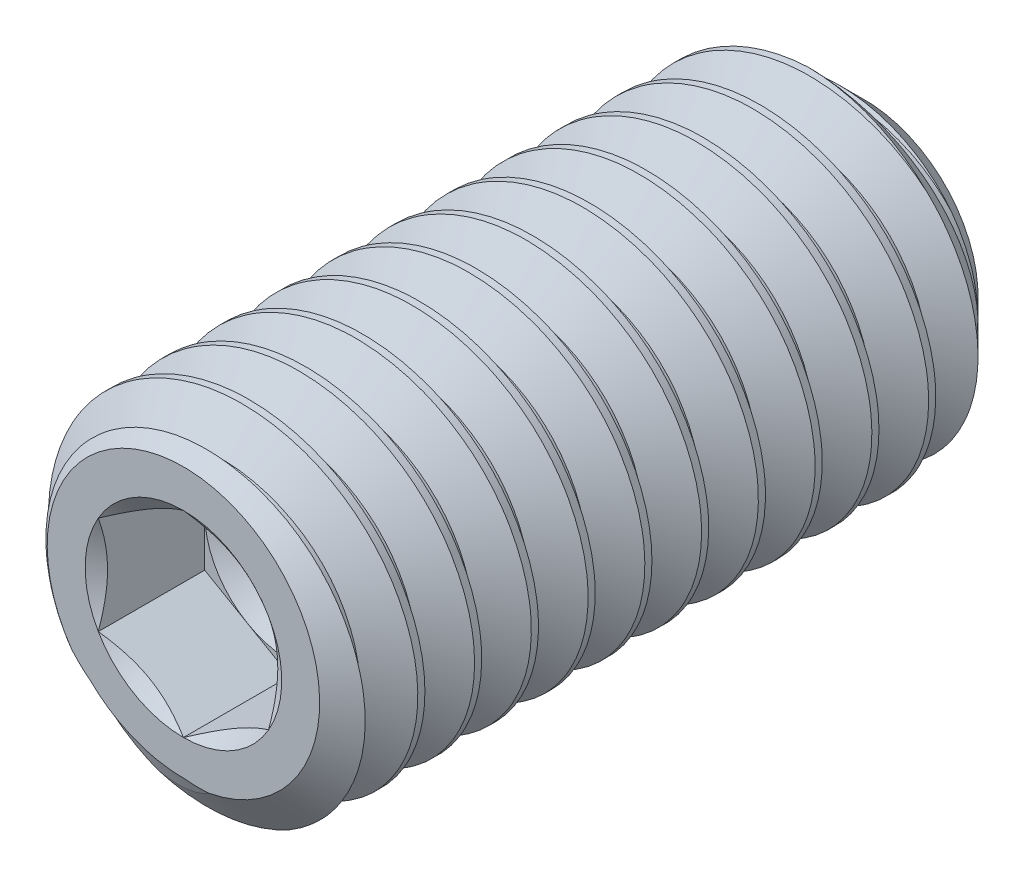
SolidWorks part; units mm, degrees
ref_plane "Front" through (0, 0, 0) normal (0, 0, 1) x (1, 0, 0)
ref_plane "Top" through (0, 0, 0) normal (0, 1, 0) x (1, 0, 0)
ref_plane "Right" through (0, 0, 0) normal (1, 0, 0) x (0, 0, -1)
sketch "Body Sketch" plane through (0, 0, 0) normal (1, 0, 0) x (0, 0, -1)
  line L0 (-3, 0) -> (-3, 1.2)
  line L1 (-3, 1.2) -> (-2.7899, 1.5)
  line L2 (-2.7899, 1.5) -> (2.5, 1.5)
  line L3 (2.5, 1.5) -> (3, 1)
  line L4 (-0.145, 1.5) -> (-0.145, -1.5) construction
  line L5 (3, 0) -> (-3, 0)
  line L6 (-3, 1.2) -> (-3, -1.2) construction
  line L7 (3, 0) -> (3, 1)
  point P11 (-0.145, 0)
  dimension "Length" = 6
  dimension "Top Chamfer" = 35
  dimension "D6" = 45
  dimension "Diameter" = 3
  dimension "D1" = 2.4
  dimension "Tip Chamfer" = 0.5
revolve "Body Revolve" add sketch "Body Sketch" angle 360 about L5
ref_plane "Bottom of Tip Plane" through (0, 0, -3) normal (0, 0, 1) x (1, 0, 0)
sketch "Spiral Sketch" plane through (0, 0, -3) normal (0, 0, 1) x (1, 0, 0)
  circle A0 centre (0, 0) radius 1.5 construction
  circle A1 centre (0, 0) radius 1.5
curve "Helix/Spiral" pitch 0.5 height 6.5 radius 1.5 centre (0, 0, -3) axis (0, 0, 1) start towards (0, 1, 0) parameters "Thread Pitch"=0.5
sketch "Cut Sweep Sketch" plane through (0, 0, 0) normal (1, 0, 0) x (0, 0, -1)
  line L0 (3, 1.5) -> (3.4375, 1.5)
  line L1 (3.4375, 1.5) -> (3.25, 1.1752)
  line L2 (3.25, 1.1752) -> (3.1875, 1.1752)
  line L3 (3.1875, 1.1752) -> (3, 1.5)
  line L4 (3.0937, 1.3376) -> (3.3438, 1.3376) construction
  line L6 (-2.7899, 1.5) -> (2.5, 1.5) construction
  dimension "D1" = 0.0625
  dimension "D3" = 60
  dimension "D2" = 0.25
sweep "Cut Sweep" cut profiles "Cut Sweep Sketch" path "Helix/Spiral" align with end faces yes
sketch "Hex Sketch" plane through (0, 0, 3) normal (0, 0, 1) x (1, 0, 0)
  line L1 (0, 0.866) -> (-0.75, 0.433)
  line L2 (-0.75, 0.433) -> (-0.75, -0.433)
  line L3 (-0.75, -0.433) -> (0, -0.866)
  line L4 (0, -0.866) -> (0.75, -0.433)
  line L5 (0.75, -0.433) -> (0.75, 0.433)
  line L6 (0.75, 0.433) -> (0, 0.866)
  circle A0 centre (0, 0) radius 0.75 construction
  dimension "Hex" = 1.5
extrude "Hex Extrude" cut sketch "Hex Sketch" against normal blind 0.9375
sketch "Hex Entry Sketch" plane through (0, 0, 3) normal (0, 0, 1) x (1, 0, 0)
  circle A0 centre (0, 0) radius 0.866
extrude "Hex Entry Extrude" cut sketch "Hex Entry Sketch" against normal through all draft 55
sketch "Hex Bottom Sketch" plane through (0, 0, 2.0625) normal (0, 0, 1) x (1, 0, 0)
  circle A0 centre (0, 0) radius 0.75 construction
  circle A1 centre (0, 0) radius 0.75
extrude "Hex Bottom Extrude" cut sketch "Hex Bottom Sketch" against normal through all draft 60
equation "\"D1@Cut Sweep Sketch\" = \"Thread Pitch@Helix/Spiral\" * .125"
equation "\"D2@Cut Sweep Sketch\" = \"Thread Pitch@Helix/Spiral\" * .5"
equation "\"D3@Helix/Spiral\" = \"Length@Body Sketch\" + \"Thread Pitch@Helix/Spiral\""
equation "\"hex Depth@Hex Extrude\" = \"Hex@Hex Sketch\" * .625"
equation "\"D1@Body Sketch\" = \"Diameter@Body Sketch\" * .8"
equation "\"Tip Chamfer@Body Sketch\" = \"Thread Pitch@Helix/Spiral\""
equation "\"Diameter\"= 3mm"
equation "\"Thread Pitch\"= 0.5mm"
equation "\"Hex Size\"= 1.5mm"
equation "\"Diameter@Body Sketch\"=\"Diameter\""
equation "\"Thread Pitch@Helix/Spiral\"     = \"Thread Pitch\""
equation "\"Hex@Hex Sketch\" = \"Hex Size\""
